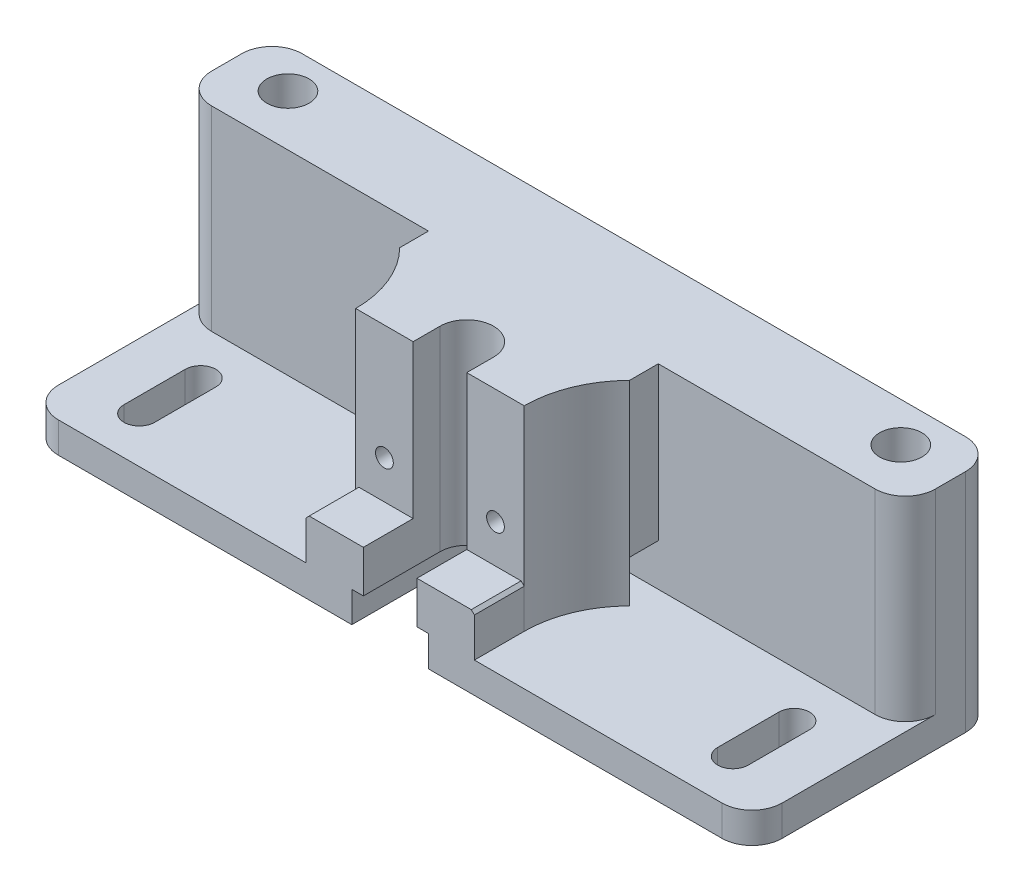
SolidWorks part; units mm, degrees
ref_plane "Front Plane" through (0, 0, 0) normal (0, 0, 1) x (1, 0, 0)
ref_plane "Top Plane" through (0, 0, 0) normal (0, 1, 0) x (1, 0, 0)
ref_plane "Right Plane" through (0, 0, 0) normal (1, 0, 0) x (0, 0, -1)
ref_plane "Plane1" through (0, 0, -20.6375) normal (0, 0, -1) x (-1, 0, 0)
sketch "Sketch1" plane through (0, 0, -20.6375) normal (0, 0, -1) x (-1, 0, 0)
  line L0 (19.05, 0) -> (19.05, 25.4)
  line L1 (19.05, 25.4) -> (-19.05, 25.4)
  line L2 (-19.05, 25.4) -> (-19.05, 0)
  line L3 (-19.05, 0) -> (19.05, 0)
extrude "Boss-Extrude1" add sketch "Sketch1" against normal blind 25.0825
ref_plane "Plane2" through (0, 0, -2.2225) normal (0, 0, 1) x (1, 0, 0)
sketch "Sketch6" plane through (0, 0, -2.2225) normal (0, 0, 1) x (1, 0, 0)
  line L0 (-6.0325, 8.1831) -> (-9.2075, 10.0162)
  line L1 (-9.2075, 10.0162) -> (-12.3825, 8.1831)
  line L2 (-12.3825, 8.1831) -> (-12.3825, 4.5169)
  line L3 (-12.3825, 4.5169) -> (-9.2075, 2.6838)
  line L4 (-9.2075, 2.6838) -> (-6.0325, 4.5169)
  line L5 (-6.0325, 4.5169) -> (-6.0325, 8.1831)
extrude "Cut-Extrude1" cut sketch "Sketch6" against normal blind 2.3876
sketch "Sketch12" plane through (0, 0, -2.2225) normal (0, 0, 1) x (1, 0, 0)
  line L0 (6.0325, 8.1831) -> (6.0325, 4.5169)
  line L1 (6.0325, 4.5169) -> (9.2075, 2.6838)
  line L2 (9.2075, 2.6838) -> (12.3825, 4.5169)
  line L3 (12.3825, 4.5169) -> (12.3825, 8.1831)
  line L4 (12.3825, 8.1831) -> (9.2075, 10.0162)
  line L5 (9.2075, 10.0162) -> (6.0325, 8.1831)
extrude "Cut-Extrude2" cut sketch "Sketch12" against normal blind 2.3876
ref_plane "Plane3" through (0, 0, 0) normal (0, -1, 0) x (-1, 0, 0)
sketch "Sketch18" plane through (0, 0, 0) normal (0, -1, 0) x (-1, 0, 0)
  line L0 (13.97, -4.445) -> (19.05, -4.445)
  line L1 (19.05, -4.445) -> (19.05, 7.9375)
  arc A0 (19.05, 7.9375) -> (13.97, -4.445) centre (31.6012, -4.445) ccw
extrude "Cut-Extrude3" cut sketch "Sketch18" against normal through all
sketch "Sketch19" plane through (0, 0, 0) normal (0, -1, 0) x (1, 0, 0)
  line L0 (4.445, 4.445) -> (-4.445, 4.445)
  line L1 (-4.445, 4.445) -> (-4.445, 0)
  line L2 (4.445, 0) -> (4.445, 4.445)
  arc A0 (-4.445, 0) -> (4.445, 0) centre (0, 0) ccw
extrude "Cut-Extrude4" cut sketch "Sketch19" against normal through all
sketch "Sketch20" plane through (0, 0, 0) normal (0, -1, 0) x (1, 0, 0)
  line L0 (19.05, -7.9375) -> (19.05, 4.445)
  line L1 (19.05, 4.445) -> (13.97, 4.445)
  arc A0 (13.97, 4.445) -> (19.05, -7.9375) centre (31.6012, 4.445) ccw
extrude "Cut-Extrude5" cut sketch "Sketch20" against normal through all
sketch "Sketch21" plane through (0, 0, 0) normal (0, -1, 0) x (1, 0, 0)
  line L0 (4.445, 0) -> (4.445, 12.7)
  line L1 (4.445, 12.7) -> (13.97, 12.7)
  line L2 (13.97, 12.7) -> (13.97, 4.445)
  line L3 (19.05, -7.9375) -> (-19.05, -7.9375)
  line L4 (-13.97, 4.445) -> (-13.97, 12.7)
  line L5 (-13.97, 12.7) -> (-4.445, 12.7)
  line L6 (-4.445, 12.7) -> (-4.445, 0)
  arc A0 (13.97, 4.445) -> (19.05, -7.9375) centre (31.6012, 4.445) ccw
  arc A1 (-19.05, -7.9375) -> (-13.97, 4.445) centre (-31.6012, 4.445) ccw
  arc A2 (-4.445, 0) -> (4.445, 0) centre (0, 0) ccw
extrude "Boss-Extrude2" add sketch "Sketch21" along normal blind 6.985
sketch "Sketch22" plane through (0, -6.985, 0) normal (0, -1, 0) x (1, 0, 0)
  line L0 (-4.445, -6.35) -> (4.445, -6.35)
  line L1 (4.445, -6.35) -> (4.445, 12.7)
  line L2 (4.445, 12.7) -> (60, 12.7)
  line L3 (60, 12.7) -> (60, -12.7)
  line L4 (60, -12.7) -> (-60, -12.7)
  line L5 (-60, -12.7) -> (-60, 12.7)
  line L6 (-60, 12.7) -> (-4.445, 12.7)
  line L7 (-4.445, 12.7) -> (-4.445, -6.35)
  point P8 (0, -12.7)
  dimension "D1" = 25.4
  dimension "D2" = 120
  dimension "D3" = 8.89
  dimension "D4" = 4.445
extrude "Boss-Extrude3" add sketch "Sketch22" along normal blind 5.08
ref_plane "Plane4" through (4.445, 0, 0) normal (-1, 0, 0) x (0, 0, 1)
sketch "Sketch29" plane through (4.445, 0, 0) normal (-1, 0, 0) x (0, 0, 1)
  line L0 (12.7, -6.985) -> (-6.35, -6.985)
  line L1 (-6.35, -6.985) -> (-6.35, -12.065)
  line L2 (-6.35, -12.065) -> (12.7, -12.065)
  line L3 (12.7, -12.065) -> (12.7, -6.985)
extrude "Cut-Extrude6" cut sketch "Sketch29" against normal blind 1.905
sketch "Sketch30" plane through (-4.445, 0, 0) normal (1, 0, 0) x (0, 0, -1)
  line L0 (-12.7, -6.985) -> (-12.7, -12.065)
  line L1 (-12.7, -12.065) -> (6.35, -12.065)
  line L2 (6.35, -12.065) -> (6.35, -6.985)
  line L3 (6.35, -6.985) -> (-12.7, -6.985)
extrude "Cut-Extrude7" cut sketch "Sketch30" against normal blind 1.905
ref_plane "Plane5" through (0, -12.065, 0) normal (0, -1, 0) x (-1, 0, 0)
sketch "Sketch48" plane through (0, -12.065, 0) normal (0, -1, 0) x (-1, 0, 0)
  line L0 (-51.7525, 5.08) -> (-51.7525, -5.08)
  line L1 (-46.6725, -5.08) -> (-46.6725, 5.08)
  arc A0 (-46.6725, 5.08) -> (-51.7525, 5.08) centre (-49.2125, 5.08) ccw
  arc A1 (-51.7525, -5.08) -> (-46.6725, -5.08) centre (-49.2125, -5.08) ccw
extrude "Cut-Extrude10" cut sketch "Sketch48" against normal up to next
sketch "Sketch57" plane through (0, -12.065, 0) normal (0, -1, 0) x (-1, 0, 0)
  line L0 (46.6725, 5.08) -> (46.6725, -5.08)
  line L1 (51.7525, -5.08) -> (51.7525, 5.08)
  arc A0 (51.7525, 5.08) -> (46.6725, 5.08) centre (49.2125, 5.08) ccw
  arc A1 (46.6725, -5.08) -> (51.7525, -5.08) centre (49.2125, -5.08) ccw
extrude "Cut-Extrude11" cut sketch "Sketch57" against normal up to next
ref_plane "Plane6" through (0, 6.35, 0) normal (0, 1, 0) x (1, 0, 0)
sketch "Sketch67" plane through (0, 6.35, 0) normal (0, 1, 0) x (1, 0, 0)
  line L0 (-7.7343, 20.6375) -> (-9.2075, 20.6375)
  line L1 (-9.2075, 20.6375) -> (-9.2075, 4.6101)
  line L2 (-9.2075, 4.6101) -> (-7.7343, 4.6101)
  line L3 (-7.7343, 4.6101) -> (-7.7343, 20.6375)
  line L4 (-9.2075, 20.6375) -> (-9.2075, 4.6101) construction
revolve "Cut-Revolve1" cut sketch "Sketch67" angle 360 about L1 reverse direction yes
sketch "Sketch77" plane through (0, 6.35, 0) normal (0, 1, 0) x (1, 0, 0)
  line L0 (10.6807, 20.6375) -> (9.2075, 20.6375)
  line L1 (9.2075, 20.6375) -> (9.2075, 4.6101)
  line L2 (9.2075, 4.6101) -> (10.6807, 4.6101)
  line L3 (10.6807, 4.6101) -> (10.6807, 20.6375)
  line L4 (9.2075, 20.6375) -> (9.2075, 4.6101) construction
revolve "Cut-Revolve2" cut sketch "Sketch77" angle 360 about L1 reverse direction yes
hole_wizard "M2.5 Clearance Hole1" positions "Sketch79" profile "Sketch78" hole size "M2.5" standard "ANSI Metric"
sketch "Sketch79" plane through (0, 0, 4.445) normal (0, 0, 1) x (1, 0, 0)
  point P0 (9.2075, 6.35)
  point P1 (-9.2075, 6.35)
sketch "Sketch78" plane through (9.2075, 6.35, 4.445) normal (1, 0, 0) x (0, -1, 0)
  line L0 (0, 0) -> (0, 25.0825)
  line L1 (0, 25.0825) -> (1.4732, 25.0825)
  line L2 (1.4732, 25.0825) -> (1.4732, 0)
  line L5 (1.4732, 0) -> (0, 0)
  line L11 (0, -6.35) -> (0, 107.95) construction
  dimension "Thru Hole Dia." = 2.9464
  dimension "Thru Hole Depth" = 25.0825
chamfer "Chamfer1" distance 0.5111 angle 45.61 1 edges at (13.97, 0, 8.5725) first distance on face at (13.97, -3.4925, 8.5725)
chamfer "Chamfer2" distance 0.5582 angle 43.977 1 edges at (-13.97, 0, 8.5725) first distance on face at (-13.97, -3.4925, 8.5725)
sketch "Sketch80" plane through (0, 0, -20.6375) normal (0, 0, -1) x (-1, 0, 0)
  line L0 (-19.05, 25.4) -> (19.05, 25.4)
  line L1 (-19.05, 25.4) -> (-19.05, 0)
  line L2 (-19.05, 0) -> (19.05, 0)
  line L3 (19.05, 25.4) -> (19.05, 0)
extrude "Cut-Extrude13" cut sketch "Sketch80" against normal up to surface (7.9375 mm away) up to face at (0, -9.525, -12.7)
sketch "Sketch81" plane through (0, 25.4, 0) normal (0, 1, 0) x (1, 0, 0)
  line L0 (-19.05, 12.7) -> (19.05, 12.7) construction
  line L1 (60, 12.7) -> (-60, 12.7)
  line L2 (60, 12.7) -> (60, 27.7)
  line L3 (60, 27.7) -> (-60, 27.7)
  line L4 (-60, 12.7) -> (-60, 27.7)
  line L5 (-60, 12.7) -> (60, 12.7) construction
  point P0 (0, 12.7)
  point P7 (0, 12.7)
  dimension "D1" = 120
  dimension "D2" = 15
extrude "Boss-Extrude4" add sketch "Sketch81" against normal up to surface (37.465 mm away) up to face at (-49.2125, -12.065, 0)
sketch "Sketch82" plane through (0, -12.065, 0) normal (0, -1, 0) x (1, 0, 0)
  line L0 (-42.1371, -21.1564) -> (42.1371, -21.1564) construction
  circle A0 centre (-50.8, -21.1564) radius 3.5
  circle A1 centre (50.8, -21.1564) radius 3.5
  point P3 (0, -21.1564)
  dimension "D1" = 50.8
  dimension "D3" = 7
  dimension "D4" = 7
  dimension "D2" = 50.8
extrude "Cut-Extrude14" cut sketch "Sketch82" against normal through all
fillet "Fillet3" radius 5 2 edges at (60, 6.6675, -27.7) (-60, 6.6675, -27.7)
fillet "Fillet4" radius 5 2 edges at (-60, 9.2075, -12.7) (60, 9.2075, -12.7)
fillet "Fillet5" radius 5 2 edges at (60, -9.525, 12.7) (-60, -9.525, 12.7)
